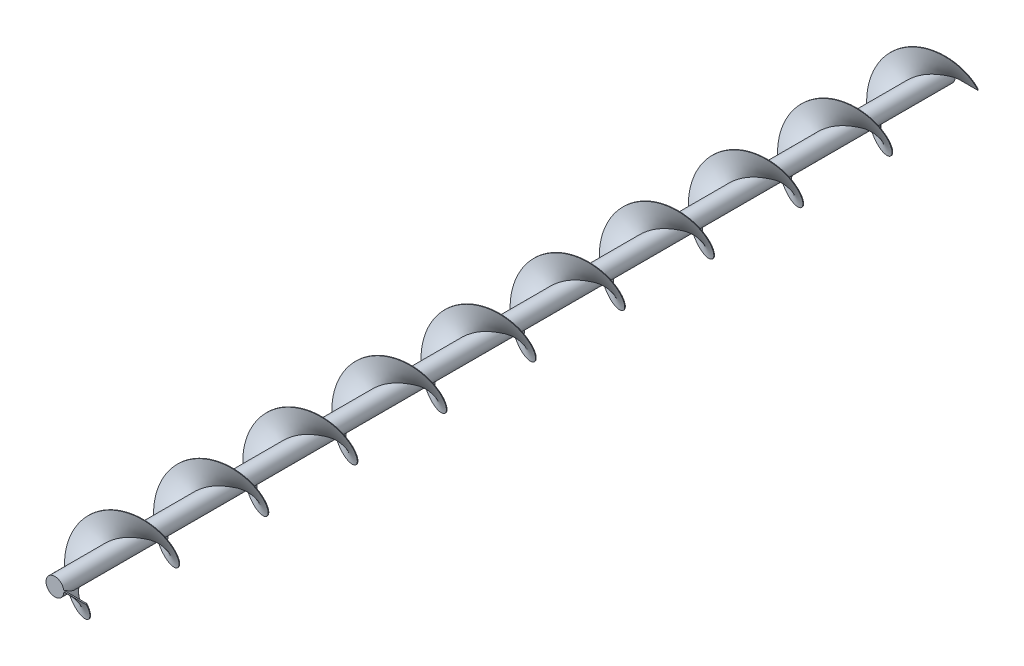
SolidWorks part; units mm, degrees
note: '?' marks a value the reader was unsure of.
material "1060 Legierung"
ref_plane "Ebene vorne" through (0, 0, 0) normal (0, 0, 1) x (1, 0, 0)
ref_plane "Ebene oben" through (0, 0, 0) normal (0, 1, 0) x (1, 0, 0)
ref_plane "Ebene rechts" through (0, 0, 0) normal (1, 0, 0) x (0, 0, -1)
sketch "Skizze1" plane through (0, 0, 0) normal (0, 0, 1) x (1, 0, 0)
  circle A0 centre (0, 0) radius 5
  dimension "D1" = 10
extrude "Aufsatz-Linear austragen1" add sketch "Skizze1" along normal blind 500
sketch "Skizze3" plane through (0, 0, 0) normal (0, 0, -1) x (-1, 0, 0)
  circle A0 centre (0, 0) radius 18.0682
curve "Spirale/Helix1" pitch 50 height 500 turns 10
sketch "Skizze5" plane through (0, 0, 0) normal (0, 0, -1) x (-1, 0, 0)
  line L1 (0, 0) -> (-17.8206, 0)
  line L2 (0, 0) -> (0, 0.7761)
  line L3 (0, 0.7761) -> (-17.8206, 0.7761)
  line L4 (-17.8206, 0) -> (-17.8206, 0.7761)
sweep "Austragung3" add profiles "Skizze5" path "Spirale/Helix1"
ref_axis "Achse1" through (0, 0, 500) along (0, 0, -1)?
